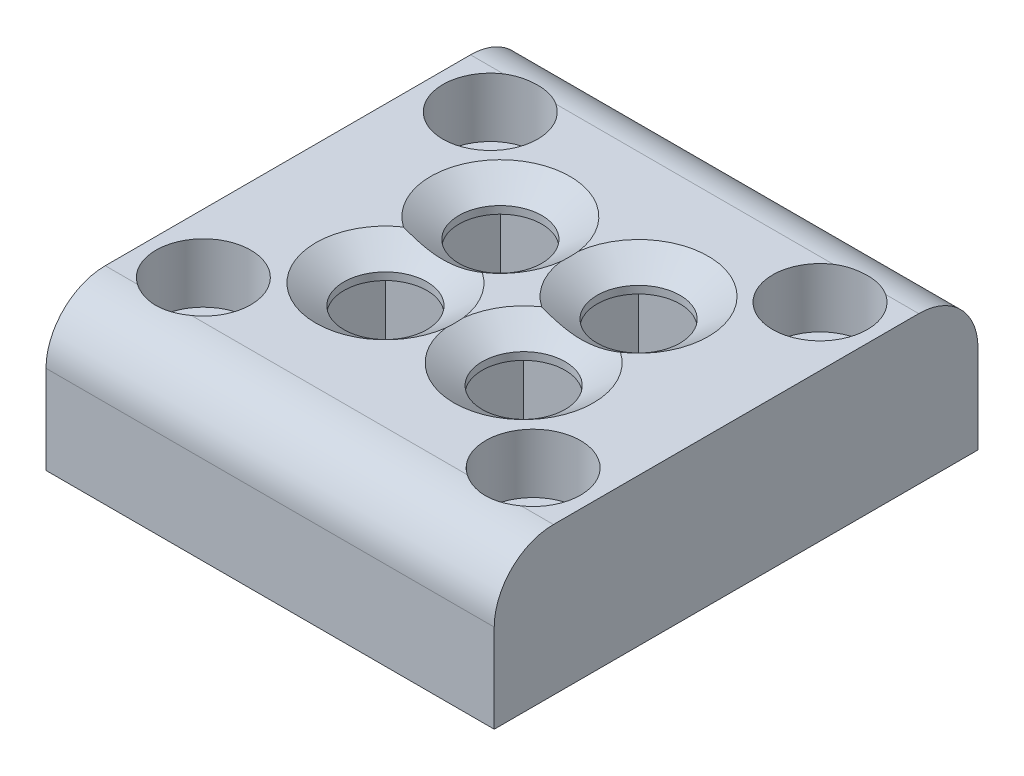
SolidWorks part; units mm, degrees
ref_plane "Front Plane" through (0, 0, 0) normal (0, 0, 1) x (1, 0, 0)
ref_plane "Top Plane" through (0, 0, 0) normal (0, 1, 0) x (1, 0, 0)
ref_plane "Right Plane" through (0, 0, 0) normal (1, 0, 0) x (0, 0, -1)
sketch "Sketch1" plane through (0, 0, 0) normal (1, 0, 0) x (0, 0, -1)
  line L0 (-12.25, -146.25) -> (12.25, -146.25)
  line L4 (-12.25, -140.25) -> (-12.25, -146.25)
  line L6 (-2.91, -138.77) -> (2.91, -138.77)
  line L8 (12.25, -140.25) -> (12.25, -146.25)
  line L9 (0, 34.0238) -> (0, -21.6118) construction
  line L10 (-12.25, -140.25) -> (-12.25, -138.77)
  line L11 (-12.25, -138.77) -> (-2.91, -138.77)
  line L12 (12.25, -140.25) -> (12.25, -138.77)
  line L13 (12.25, -138.77) -> (2.91, -138.77)
  point P4 (-12.25, -143.25)
  dimension "D1" = 7.48
  dimension "D2" = 6
  dimension "D3" = 24.5
  dimension "D5" = 5.82
  dimension "D7" = 143.25
extrude "Boss-Extrude1" add sketch "Sketch1" along normal blind 22.7
sketch "Sketch2" plane through (0, -138.77, 0) normal (0, 1, 0) x (1, 0, 0)
  line L0 (0, 2.91) -> (7.85, 2.91)
  line L2 (22.7, 2.91) -> (14.85, 2.91)
  line L3 (0, -2.91) -> (7.85, -2.91)
  line L5 (22.7, -12.25) -> (0, -12.25) construction
  line L6 (14.85, -2.91) -> (22.7, -2.91)
  line L7 (22.7, 12.25) -> (0, 12.25) construction
  line L8 (22.7, 12.25) -> (22.7, -12.25) construction
  circle A0 centre (14.85, 2.91) radius 2.1
  circle A1 centre (7.85, 2.91) radius 2.1
  circle A2 centre (14.85, -2.91) radius 2.1
  circle A3 centre (7.85, -2.91) radius 2.1
  point P11 (0, 0)
  dimension "D1" = 9.34
  dimension "D2" = 9.34
  dimension "D3" = 7
  dimension "D4" = 7.85
extrude "Cut-Extrude1" cut sketch "Sketch2" against normal blind 22.7 contours A2 | A0 | A1 | A3
sketch "Sketch4" plane through (0, -146.25, 0) normal (0, -1, 0) x (1, 0, 0)
  line L0 (22.7, 12.25) -> (22.7, -12.25) construction
  line L1 (0, 12.25) -> (0, -12.25) construction
  line L2 (22.7, 12.25) -> (0, 12.25) construction
  line L8 (5.6, 0.66) -> (10.1, 0.66)
  line L9 (5.6, 0.66) -> (5.6, 5.16)
  line L10 (5.6, 5.16) -> (10.1, 5.16)
  line L11 (10.1, 0.66) -> (10.1, 5.16)
  line L12 (5.6, 0.66) -> (10.1, 5.16) construction
  line L13 (5.6, 5.16) -> (10.1, 0.66) construction
  line L14 (12.6, 0.66) -> (17.1, 0.66)
  line L15 (12.6, 0.66) -> (12.6, 5.16)
  line L16 (12.6, 5.16) -> (17.1, 5.16)
  line L17 (17.1, 0.66) -> (17.1, 5.16)
  line L18 (12.6, 0.66) -> (17.1, 5.16) construction
  line L19 (12.6, 5.16) -> (17.1, 0.66) construction
  line L20 (17.1, -0.66) -> (12.6, -0.66)
  line L21 (17.1, -0.66) -> (17.1, -5.16)
  line L22 (17.1, -5.16) -> (12.6, -5.16)
  line L23 (12.6, -0.66) -> (12.6, -5.16)
  line L24 (17.1, -0.66) -> (12.6, -5.16) construction
  line L25 (17.1, -5.16) -> (12.6, -0.66) construction
  line L26 (10.1, -0.66) -> (5.6, -0.66)
  line L27 (10.1, -0.66) -> (10.1, -5.16)
  line L28 (10.1, -5.16) -> (5.6, -5.16)
  line L29 (5.6, -0.66) -> (5.6, -5.16)
  line L30 (10.1, -0.66) -> (5.6, -5.16) construction
  line L31 (10.1, -5.16) -> (5.6, -0.66) construction
  point P2 (7.85, 2.91)
  point P21 (14.85, 2.91)
  point P26 (14.85, -2.91)
  point P31 (7.85, -2.91)
  dimension "D1" = 4.5
  dimension "D2" = 7.85
  dimension "D3" = 5.82
  dimension "D4" = 7
  dimension "D5" = 7.85
  dimension "D6" = 7
  dimension "D7" = 9.34
extrude "Cut-Extrude2" cut sketch "Sketch4" against normal blind 6.1
sketch "Sketch7" plane through (0, -138.77, 0) normal (0, -1, 0) x (-1, 0, 0)
  line L0 (-22.7, 12.25) -> (0, 12.25) construction
  line L1 (-22.7, -12.25) -> (-22.7, 12.25) construction
  circle A0 centre (-3, -7.28) radius 1.5
  circle A1 centre (-19.7, -7.28) radius 1.5
  circle A2 centre (-19.7, 7.25) radius 1.5
  circle A3 centre (-3, 7.25) radius 1.5
  dimension "D1" = 14.53
  dimension "D2" = 5
  dimension "D3" = 16.7
  dimension "D4" = 3
extrude "Cut-Extrude3" cut sketch "Sketch7" along normal blind 13
sketch "Sketch9" plane through (0, -138.77, 0) normal (0, 1, 0) x (1, 0, 0)
  circle A0 centre (3, 7.25) radius 2.4
  circle A1 centre (19.7, 7.25) radius 2.4
  circle A2 centre (19.7, -7.28) radius 2.4
  circle A3 centre (3, -7.28) radius 2.4
extrude "Cut-Extrude4" cut sketch "Sketch9" against normal blind 3
sketch "Sketch10" plane through (22.7, 0, 0) normal (1, 0, 0) x (0, 0, -1)
  line L0 (12.25, -135) -> (-12.25, -135)
  line L1 (12.25, -135) -> (12.25, -134.4431)
  line L2 (-12.25, -135) -> (-12.25, -134.4431)
  arc A2 (-12.25, -134.4431) -> (12.25, -134.4431) centre (0, 0) ccw
  point P5 (0, -135)
fillet "Fillet1" radius 3 2 edges at (11.35, -138.77, 12.25) (11.35, -138.77, -12.25)
chamfer "Chamfer2" distance 1 angle 55 4 edges at (14.85, -138.77, 5.01) (14.85, -138.77, -0.81) (7.85, -138.77, -0.81) (7.85, -138.77, 5.01) first distance on face at (14.85, -140.15, 5.01) first distance on face at (14.85, -140.15, -0.81) first distance on face at (7.85, -140.15, -0.81) first distance on face at (7.85, -140.15, 5.01)
